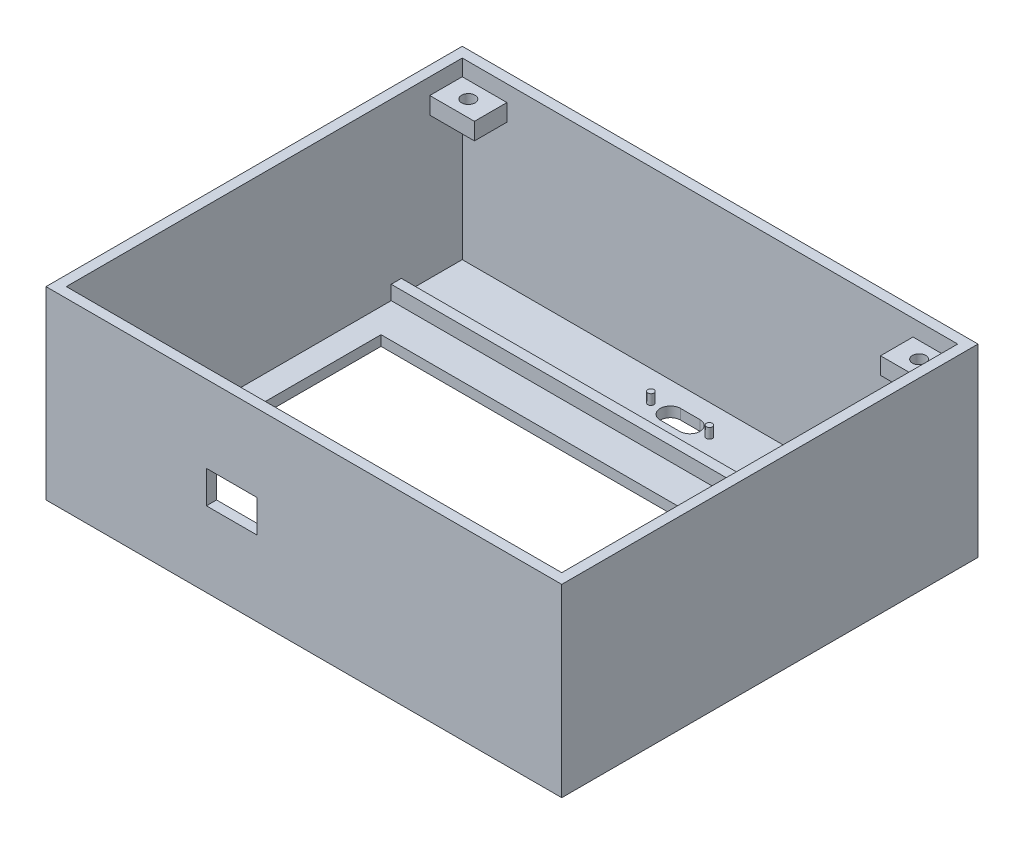
SolidWorks part; units mm, degrees
ref_plane "Front Plane" through (0, 0, 0) normal (0, 0, 1) x (1, 0, 0)
ref_plane "Top Plane" through (0, 0, 0) normal (0, 1, 0) x (1, 0, 0)
ref_plane "Right Plane" through (0, 0, 0) normal (1, 0, 0) x (0, 0, -1)
sketch "Sketch1" plane through (0, 0, 0) normal (0, 1, 0) x (1, 0, 0)
  line L1 (0, 0) -> (127, 0)
  line L2 (0, 0) -> (0, 85)
  line L3 (0, 85) -> (127, 85)
  line L4 (127, 0) -> (127, 85)
extrude "Boss-Extrude1" add sketch "Sketch1" along normal blind 2.5
sketch "Sketch2" plane through (0, 2.5, 0) normal (0, 1, 0) x (1, 0, 0)
  line L0 (0, 85) -> (127, 85)
  line L1 (127, 85) -> (127, 0)
  line L2 (127, 0) -> (0, 0)
  line L3 (0, 0) -> (0, 85)
  line L5 (2.5, 82.5) -> (124.5, 82.5)
  line L6 (2.5, 82.5) -> (2.5, 2.5)
  line L7 (2.5, 2.5) -> (124.5, 2.5)
  line L8 (124.5, 82.5) -> (124.5, 2.5)
  dimension "D1" = 2.5
  dimension "D2" = 2.5
  dimension "D3" = 2.5
  dimension "D4" = 2.5
extrude "Boss-Extrude2" add sketch "Sketch2" along normal blind 38.5
sketch "Sketch3" plane through (0, 0, 0) normal (0, -1, 0) x (-1, 0, 0)
  line L0 (-127, 85) -> (0, 85) construction
  line L1 (-8.5, 5.5) -> (-118.5, 5.5)
  line L2 (-8.5, 5.5) -> (-8.5, 74)
  line L3 (-8.5, 74) -> (-118.5, 74)
  line L4 (-118.5, 5.5) -> (-118.5, 74)
  line L6 (0, 0) -> (-127, 0) construction
  line L7 (-127, 0) -> (-127, 85) construction
  line L8 (0, 85) -> (0, 0) construction
  dimension "D1" = 11
  dimension "D2" = 5.5
  dimension "D3" = 8.5
  dimension "D4" = 8.5
extrude "Cut-Extrude1" cut sketch "Sketch3" against normal blind 2.5
sketch "Sketch6" plane through (0, 0, 0) normal (0, -1, 0) x (-1, 0, 0)
  line L8 (-61.1, 92.6537) -> (-65.9, 92.6537) construction
  line L9 (-61.1, 90.1537) -> (-65.9, 90.1537)
  line L10 (-61.1, 95.1537) -> (-65.9, 95.1537)
  arc A0 (-61.1, 90.1537) -> (-61.1, 95.1537) centre (-61.1, 92.6537) ccw
  arc A2 (-65.9, 95.1537) -> (-65.9, 90.1537) centre (-65.9, 92.6537) ccw
  point P1 (-63.5, 92.6537)
sketch "Sketch9" plane through (0, 0, -85) normal (0, 0, -1) x (-1, 0, 0)
  line L0 (-127, 0) -> (0, 0) construction
  line L1 (-127, 0) -> (0, 0)
  line L2 (-127, 0) -> (-127, 2.5)
  line L4 (0, 0) -> (0, 2.5)
  line L5 (-127, 41) -> (-127, 0) construction
  line L6 (0, 41) -> (0, 0) construction
  line L7 (-2.5, 2.5) -> (-124.5, 2.5)
  line L8 (-127, 41) -> (-124.5, 41)
  line L9 (-127, 41) -> (-127, 2.5)
  line L11 (-124.5, 41) -> (-124.5, 2.5)
  line L12 (0, 41) -> (-2.5, 41)
  line L13 (0, 41) -> (0, 2.5)
  line L15 (-2.5, 41) -> (-2.5, 2.5)
  dimension "D2" = 2.5
  dimension "D3" = 2.5
extrude "Boss-Extrude3" add sketch "Sketch9" along normal blind 15
sketch "Sketch10" plane through (0, 41, 0) normal (0, 1, 0) x (1, 0, 0)
  line L1 (2.5, 85) -> (124.5, 85)
  line L2 (2.5, 85) -> (2.5, 82.5)
  line L3 (2.5, 82.5) -> (124.5, 82.5)
  line L4 (124.5, 85) -> (124.5, 82.5)
extrude "Cut-Extrude2" cut sketch "Sketch10" against normal blind 35
sketch "Sketch11" plane through (0, 0, -100) normal (0, 0, -1) x (-1, 0, 0)
  line L1 (0, 0) -> (-127, 0)
  line L2 (0, 0) -> (0, 41)
  line L3 (0, 41) -> (-127, 41)
  line L4 (-127, 0) -> (-127, 41)
extrude "Boss-Extrude4" add sketch "Sketch11" along normal blind 2.5
sketch "Sketch13" plane through (0, 2.5, 0) normal (0, 1, 0) x (1, 0, 0)
  circle A0 centre (56.3, 92.6537) radius 0.75
  circle A1 centre (70.7, 92.6537) radius 0.75
  arc A2 (61.1, 95.1537) -> (61.1, 90.1537) centre (61.1, 92.6537) ccw construction
  dimension "D1" = 14.4
  dimension "D2" = 4.8
  dimension "D3" = 4.8
  dimension "D4" = 1.5
  dimension "D5" = 1.5
extrude "Cut-Extrude4" cut sketch "Sketch6" against normal blind 2.5
sketch "Sketch14" plane through (0, 2.5, 0) normal (0, 1, 0) x (1, 0, 0)
  line L1 (56, 87.1537) -> (71, 87.1537)
  line L2 (56, 87.1537) -> (56, 86.1537)
  line L3 (56, 86.1537) -> (71, 86.1537)
  line L4 (71, 87.1537) -> (71, 86.1537)
  arc A0 (61.1, 95.1537) -> (61.1, 90.1537) centre (61.1, 92.6537) ccw construction
  arc A1 (65.9, 90.1537) -> (65.9, 95.1537) centre (65.9, 92.6537) ccw construction
  dimension "D1" = 5.1
  dimension "D2" = 5.1
extrude "Cut-Extrude5" cut sketch "Sketch14" against normal blind 1.5
extrude "Boss-Extrude6" add sketch "Sketch13" along normal blind 2.5
sketch "Sketch17" plane through (0, 0, 0) normal (0, 0, 1) x (1, 0, 0)
  line L0 (0, 41) -> (0, 0) construction
  line L1 (39.5, 26.5) -> (52, 26.5)
  line L2 (39.5, 26.5) -> (39.5, 18.5)
  line L3 (39.5, 18.5) -> (52, 18.5)
  line L4 (52, 26.5) -> (52, 18.5)
  line L5 (0, 0) -> (127, 0) construction
  dimension "D1" = 39.5
  dimension "D2" = 18.5
  dimension "D3" = 8
  dimension "D4" = 12.5
extrude "Cut-Extrude6" cut sketch "Sketch17" against normal blind 2.5
sketch "Sketch19" plane through (0, 41, 0) normal (0, 1, 0) x (1, 0, 0)
  line L0 (0, 102.5) -> (127, 102.5)
  line L1 (127, 102.5) -> (127, 0)
  line L2 (127, 0) -> (0, 0)
  line L3 (0, 0) -> (0, 102.5)
  line L5 (2.5, 100) -> (124.5, 100)
  line L6 (2.5, 100) -> (2.5, 2.5)
  line L7 (2.5, 2.5) -> (124.5, 2.5)
  line L8 (124.5, 100) -> (124.5, 2.5)
extrude "Boss-Extrude7" add sketch "Sketch19" along normal blind 4.5
sketch "Sketch20" plane through (0, 0, -100) normal (0, 0, 1) x (1, 0, 0)
  line L0 (2.5, 45.5) -> (2.5, 2.5) construction
  line L1 (2.5, 41.5) -> (13.5, 41.5)
  line L2 (2.5, 41.5) -> (2.5, 37.3158)
  line L3 (2.5, 37.3158) -> (13.5, 37.3158)
  line L4 (13.5, 41.5) -> (13.5, 37.3158)
  line L5 (124.5, 45.5) -> (2.5, 45.5) construction
  line L6 (113.5, 37.3158) -> (124.5, 37.3158)
  line L7 (113.5, 41.5) -> (113.5, 37.3158)
  line L8 (113.5, 41.5) -> (124.5, 41.5)
  line L9 (124.5, 41.5) -> (124.5, 37.3158)
  dimension "D1" = 4
  dimension "D2" = 11
extrude "Boss-Extrude8" add sketch "Sketch20" along normal blind 8
sketch "Sketch22" plane through (0, 41.5, 0) normal (0, 1, 0) x (1, 0, 0)
  line L0 (124.5, 2.5) -> (124.5, 100) construction
  line L2 (2.5, 92) -> (2.5, 100) construction
  line L5 (13.5, 100) -> (2.5, 100) construction
  circle A0 centre (8, 96) radius 1.65
  circle A1 centre (119, 96) radius 1.65
  dimension "D1" = 4
  dimension "D2" = 5.5
  dimension "D4" = 5.5
  dimension "D5" = 3.3
  dimension "D3" = 2
extrude "Cut-Extrude7" cut sketch "Sketch22" against normal blind 5
